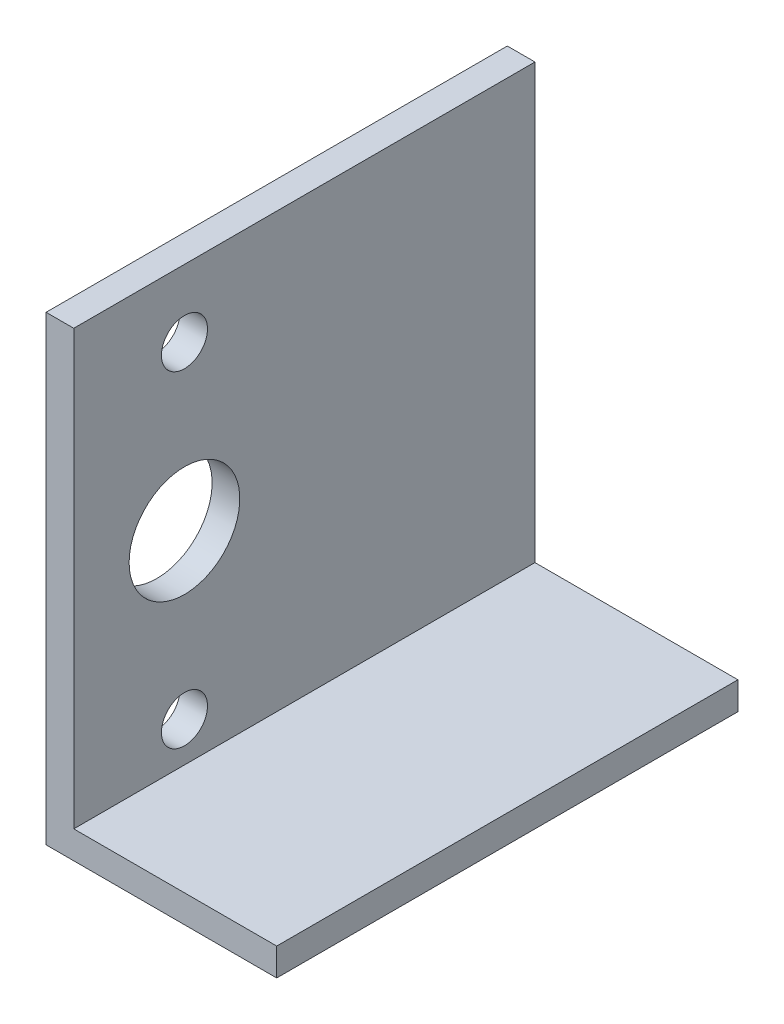
SolidWorks part; units mm, degrees
ref_plane "Alzado" through (0, 0, 0) normal (0, 0, 1) x (1, 0, 0)
ref_plane "Planta" through (0, 0, 0) normal (0, 1, 0) x (1, 0, 0)
ref_plane "Vista lateral" through (0, 0, 0) normal (1, 0, 0) x (0, 0, -1)
sketch "Croquis1" plane through (0, 0, 0) normal (0, 0, 1) x (1, 0, 0)
  line L0 (0, 50) -> (0, 0)
  line L1 (0, 0) -> (25, 0)
  line L2 (3, 50) -> (3, 3)
  line L3 (3, 3) -> (25, 3)
  line L4 (0, 50) -> (3, 50)
  line L5 (25, 0) -> (25, 3)
  dimension "D1" = 50
  dimension "D2" = 25
  dimension "D3" = 3
extrude "Saliente-Extruir1" add sketch "Croquis1" along normal blind 50
sketch "Croquis2" plane through (0, 0, 0) normal (-1, 0, 0) x (0, 0, 1)
  line L0 (38, 50) -> (38, 0) construction
  line L1 (50, 50) -> (0, 50) construction
  line L2 (50, 0) -> (0, 0) construction
  line L3 (50, 50) -> (50, 0) construction
  line L4 (0, 25) -> (50, 25) construction
  line L5 (0, 50) -> (0, 0) construction
  circle A0 centre (38, 25) radius 6
  circle A1 centre (38, 42.7) radius 2.5
  circle A2 centre (38, 7.3) radius 2.5
  point P20 (37.2151, 25)
  dimension "D3" = 12
  dimension "D6" = 5
  dimension "D1" = 12
  dimension "D2" = 25
  dimension "D4" = 35.4
  dimension "D5" = 17.7
extrude "Cortar-Extruir1" cut sketch "Croquis2" against normal up to surface (3 mm away) up to face at (3, 26.5, 25)
equation "\"D5@Croquis2\"=\"D4@Croquis2\"/2"
